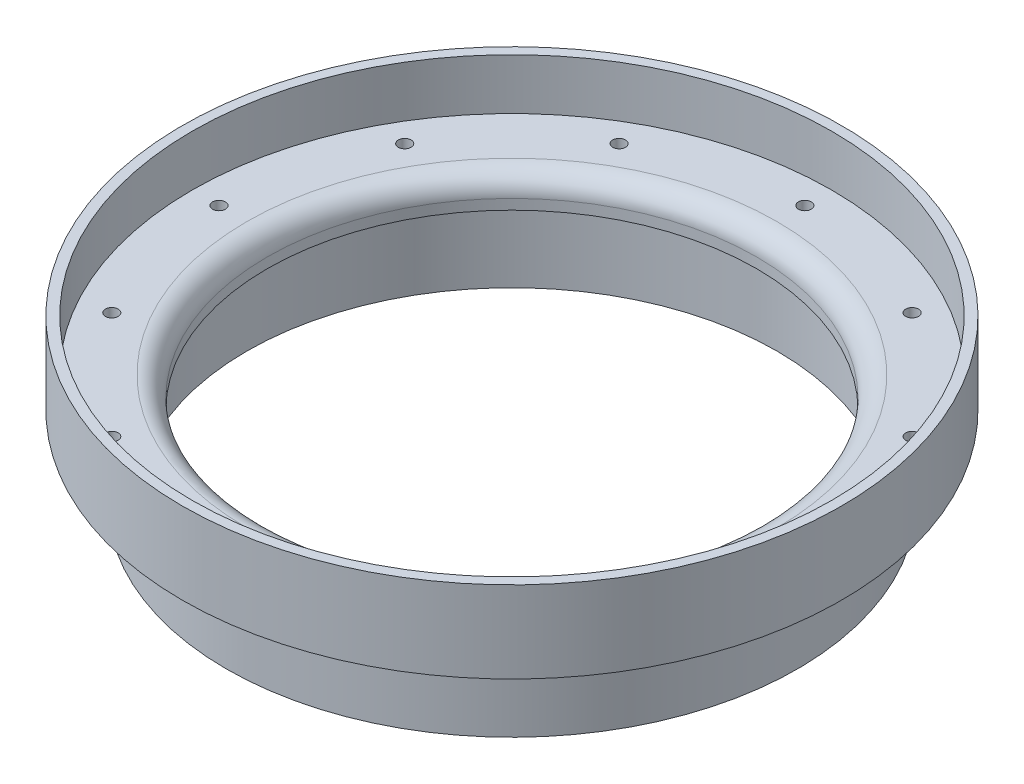
SolidWorks part; units mm, degrees
material "6061-T6 (SS)"
ref_plane "Front Plane" through (0, 0, 0) normal (0, 0, 1) x (1, 0, 0)
ref_plane "Top Plane" through (0, 0, 0) normal (0, 1, 0) x (1, 0, 0)
ref_plane "Right Plane" through (0, 0, 0) normal (1, 0, 0) x (0, 0, -1)
ref_axis "Axis1" through (0, 55, 0) along (0, -1, 0)
sketch "Cross Section" plane through (0, 0, 0) normal (0, 0, 1) x (1, 0, 0)
  line L0 (-38.1, -1.5875) -> (-38.1, -3.175)
  line L1 (-38.1, -3.175) -> (-41.275, -3.175)
  line L2 (-41.275, -3.175) -> (-41.275, -15.875)
  line L4 (0, -15.875) -> (-38.1, -15.875) construction
  line L5 (-44.45, -15.875) -> (-44.45, -3.175)
  line L6 (-44.45, -3.175) -> (-51.308, -3.175)
  line L7 (-51.308, -3.175) -> (-51.308, 9.525)
  line L8 (-51.308, 9.525) -> (-49.784, 9.525)
  line L9 (-49.784, 9.525) -> (-49.784, 1.5875)
  line L11 (-38.1, 0) -> (0, 0) construction
  line L13 (-44.45, -15.875) -> (-41.275, -15.875)
  line L14 (-49.784, 1.5875) -> (-49.784, 3.175) construction
  line L15 (-41.275, 1.5875) -> (-49.784, 1.5875)
  arc A0 (-41.275, 1.5875) -> (-38.1, -1.5875) centre (-41.275, -1.5875) cw
  point P16 (0, 0)
  dimension "D2" = 3.175
  dimension "D1" = 3.175
  dimension "D3" = 3.175
  dimension "D5" = 6.858
  dimension "D6" = 12.7
  dimension "D9" = 3.175
  dimension "D4" = 1.5875
  dimension "D7" = 38.1
revolve "Main" add sketch "Cross Section" angle 360 about axis through (0, 55, 0) along (0, -1, 0)
sketch "Hole Location" plane through (0, 0, 0) normal (0, 1, 0) x (1, 0, 0)
  line L0 (0, 0) -> (-45.6057, 0) construction
  circle A0 centre (0, 0) radius 45.6057 construction
  dimension "D1" = 91.2114
hole_wizard "#3-48 Tapped Hole1" positions "Sketch1" profile "Sketch2" tap size "#3-48" standard "ANSI Inch" end condition through all
sketch "Sketch1" plane through (0, 1.5875, 0) normal (0, 1, 0) x (1, 0, 0)
  point P0 (-45.6057, 0)
sketch "Sketch2" plane through (-45.6057, 1.5875, 0) normal (1, 0, 0) x (0, 0, 1)
  line L0 (0, 0) -> (0, 17.4625)
  line L1 (0, 17.4625) -> (0.9969, 17.4625)
  line L2 (0.9969, 17.4625) -> (0.9969, 0)
  line L5 (0.9969, 0) -> (0, 0)
  line L11 (0, -6.35) -> (0, 107.95) construction
  dimension "Thru Tap Drill Dia." = 1.9939
  dimension "Thru Tap Drill Depth" = 17.4625
cosmetic thread "Hole Thread1" parameters "D2"=2.5146
pattern_circular "CirPattern1" count 12 over 360 of "#3-48 Tapped Hole1"
equation "\"D1@Hole Location\"=\"TANK DIAMETER@Cryo Tank.Assembly\"+\"GASKET SEAT THICKNESS@Cryo Tank.Assembly\"+\"LINER THICKNESS@Cryo Tank.Assembly\"+\"SHRINK FIT DELTA@Cryo Tank.Assembly\""
equation "\"D1@Cross Section\"=\"LINER THICKNESS@Cryo Tank.Assembly\""
equation "\"D3@Cross Section\"=\"ALUMINUM LAP THICKNESS@Cryo Tank.Assembly\""
equation "\"D5@Cross Section\"=2*\"CF THICKNESS@Cryo Tank.Assembly\"+\"NOMEX THICKNESS@Cryo Tank.Assembly\""
equation "\"D7@Cross Section\"=\"TANK DIAMETER@Cryo Tank.Assembly\"/2"
